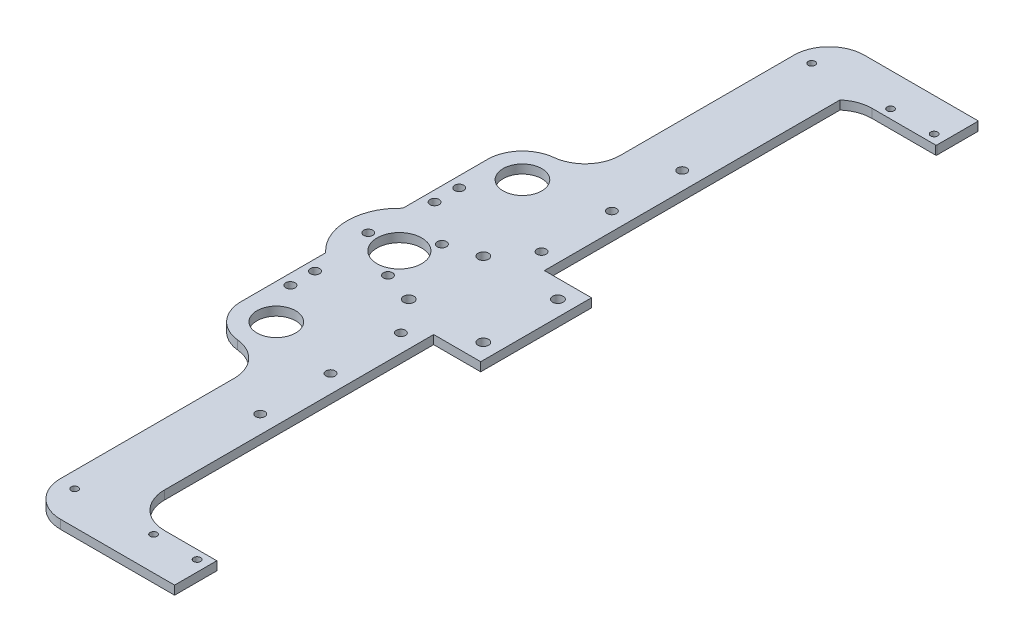
SolidWorks part; units mm, degrees
ref_plane "Front Plane" through (0, 0, 0) normal (0, 0, 1) x (1, 0, 0)
ref_plane "Top Plane" through (0, 0, 0) normal (0, 1, 0) x (1, 0, 0)
ref_plane "Right Plane" through (0, 0, 0) normal (1, 0, 0) x (0, 0, -1)
sketch "Sketch1" plane through (0, 0, 0) normal (0, 1, 0) x (1, 0, 0)
  line L0 (-67.9713, -52.7283) -> (-67.9713, -82.5864)
  line L6 (-67.9713, 4.9919) -> (-67.9713, -24.8662)
  line L14 (-22.9035, 106.3552) -> (-32.5284, 106.3552)
  line L17 (8.6823, 106.3552) -> (-7.1106, 106.3552)
  line L20 (-32.5284, -183.9497) -> (7.3984, -183.9497)
  line L22 (-22.9035, 106.3552) -> (8.6823, 106.3552)
  line L24 (-14.5158, 91.1152) -> (8.6823, 91.1152)
  line L26 (7.3984, -183.9497) -> (8.6823, -183.9497)
  line L28 (-10.2035, -168.7097) -> (8.6823, -168.7097)
  line L30 (8.6823, -168.7097) -> (8.6823, -183.9497)
  line L31 (-45.2284, -108.5097) -> (-45.2284, -171.2497)
  line L32 (8.6823, 106.3552) -> (8.6823, 91.1152)
  line L33 (-45.2284, 93.6552) -> (-45.2284, 30.9152)
  line L34 (-22.9035, -156.0097) -> (-22.9035, -58.7973)
  line L35 (-22.9035, -38.7973) -> (-5.9035, -38.7973) construction
  line L37 (-22.9035, -58.7973) -> (-22.9035, -64.1973)
  line L40 (-5.9035, -38.7973) -> (-5.9035, -18.7973)
  line L41 (-5.9035, -38.7973) -> (-5.9035, -58.7973)
  line L42 (-5.9035, -18.7973) -> (-22.9035, -18.7973)
  line L43 (-5.9035, -58.7973) -> (-22.9035, -58.7973)
  line L44 (-22.9035, -18.7973) -> (-22.9035, 87.9512)
  arc A0 (-67.9713, -82.5864) -> (-56.6084, -95.8785) centre (-55.2885, -83.2473) ccw
  arc A1 (-45.2284, -108.5097) -> (-56.6084, -95.8785) centre (-57.9284, -108.5097) ccw
  arc A4 (-56.6084, 18.284) -> (-45.2284, 30.9152) centre (-57.9284, 30.9152) ccw
  arc A5 (-56.6084, 18.284) -> (-67.9713, 4.9919) centre (-55.2885, 5.6527) ccw
  arc A6 (-67.9713, -24.8662) -> (-67.9713, -52.7283) centre (-55.2885, -38.7973) ccw
  arc A22 (-45.2284, 93.6552) -> (-32.5284, 106.3552) centre (-32.5284, 93.6552) cw
  arc A23 (-45.2284, -171.2497) -> (-32.5284, -183.9497) centre (-32.5284, -171.2497) ccw
  arc A24 (-22.9035, 87.9512) -> (-14.5158, 91.1152) centre (-14.5158, 78.4152) cw
  arc A25 (-22.9035, -156.0097) -> (-10.2035, -168.7097) centre (-10.2035, -156.0097) ccw
  circle A30 centre (-55.2885, -83.2473) radius 6.985 construction
  circle A31 centre (-64.1613, -69.2773) radius 1.65 construction
  circle A32 centre (-64.1613, -60.3873) radius 1.65 construction
  circle A33 centre (-55.2885, -38.7973) radius 8.0645 construction
  circle A34 centre (-49.6688, -29.0636) radius 1.65 construction
  circle A35 centre (-49.6688, -48.531) radius 1.65 construction
  circle A36 centre (-66.528, -38.7973) radius 1.65 construction
  circle A37 centre (-64.1613, -17.2073) radius 1.65 construction
  circle A38 centre (-64.1613, -8.3173) radius 1.65 construction
  circle A39 centre (-55.2885, 5.6527) radius 6.985 construction
  circle A40 centre (-55.2885, -83.2473) radius 6.985
  circle A41 centre (-64.1613, -69.2773) radius 1.65
  circle A42 centre (-64.1613, -60.3873) radius 1.65
  circle A43 centre (-55.2885, -38.7973) radius 8.0645
  circle A44 centre (-49.6688, -29.0636) radius 1.65
  circle A45 centre (-49.6688, -48.531) radius 1.65
  circle A46 centre (-66.528, -38.7973) radius 1.65
  circle A47 centre (-64.1613, -17.2073) radius 1.65
  circle A48 centre (-64.1613, -8.3173) radius 1.65
  circle A49 centre (-55.2885, 5.6527) radius 6.985
  circle A50 centre (-29.342, 37.4027) radius 1.65 construction
  circle A51 centre (-29.342, 12.0027) radius 1.65 construction
  circle A52 centre (-29.342, -13.3973) radius 1.65 construction
  circle A54 centre (-29.342, -64.1973) radius 1.65 construction
  circle A55 centre (-29.342, -89.5973) radius 1.65 construction
  circle A56 centre (-29.342, -114.9973) radius 1.65 construction
  circle A57 centre (-29.342, 37.4027) radius 1.65
  circle A58 centre (-29.342, 12.0027) radius 1.65
  circle A59 centre (-29.342, -13.3973) radius 1.65
  circle A61 centre (-29.342, -64.1973) radius 1.65
  circle A62 centre (-29.342, -89.5973) radius 1.65
  circle A63 centre (-29.342, -114.9973) radius 1.65
  point P58 (-45.2284, 106.3552)
  dimension "D5" = 15.24
  dimension "D6" = 15.24
  dimension "D7" = 62.74
  dimension "D8" = 62.74
  dimension "D44" = 12.7
  dimension "D46" = 12.7
  dimension "D47" = 12.7
  dimension "D1" = 17
  dimension "D2" = 20
  dimension "D36" = 22.3249
extrude "Boss-Extrude1" add sketch "Sketch1" along normal blind 3.175 contours A25 A24 L24 L32 L17 L22 L14 A22 A4 A5 L6 A6 L0 A0 A1 A23 L20 L26 L30 L28 A63 A62 A61 A59 A58 A57 A49 A48 A47 A46 region at (-34.9503, 0, 39.1232)
fillet "Fillet2" radius 0.254 2 edges at (8.6823, 1.5875, -91.1152) (8.6823, 1.5875, -106.3552)
sketch "Sketch4" plane through (0, 3.175, 0) normal (0, 1, 0) x (1, 0, 0)
  circle A0 centre (4.754, 94.2902) radius 1.25
  circle A1 centre (-10.971, 94.2902) radius 1.25
  circle A2 centre (-39.471, 94.2902) radius 1.25
  circle A3 centre (-39.471, -171.8847) radius 1.25
  circle A4 centre (-10.971, -171.8847) radius 1.25
  circle A5 centre (4.754, -171.8847) radius 1.25
extrude "Cut-Extrude1" cut sketch "Sketch4" against normal through all
sketch "Sketch5" plane through (0, 3.175, 0) normal (0, 1, 0) x (1, 0, 0)
  circle A1 centre (-11.5006, -25.3269) radius 1.8986
  circle A2 centre (-38.4414, -25.3269) radius 1.8986
  circle A5 centre (-38.4414, -52.2677) radius 1.8986
  circle A6 centre (-11.5006, -52.2677) radius 1.8986
  point P9 (-38.4414, -52.2677)
  point P17 (-11.5006, -52.2677)
  point P18 (-11.5006, -25.3269)
  point P19 (-38.4414, -52.2677)
  dimension "D1" = 3.7973
extrude "Cut-Extrude2" cut sketch "Sketch5" against normal through all
